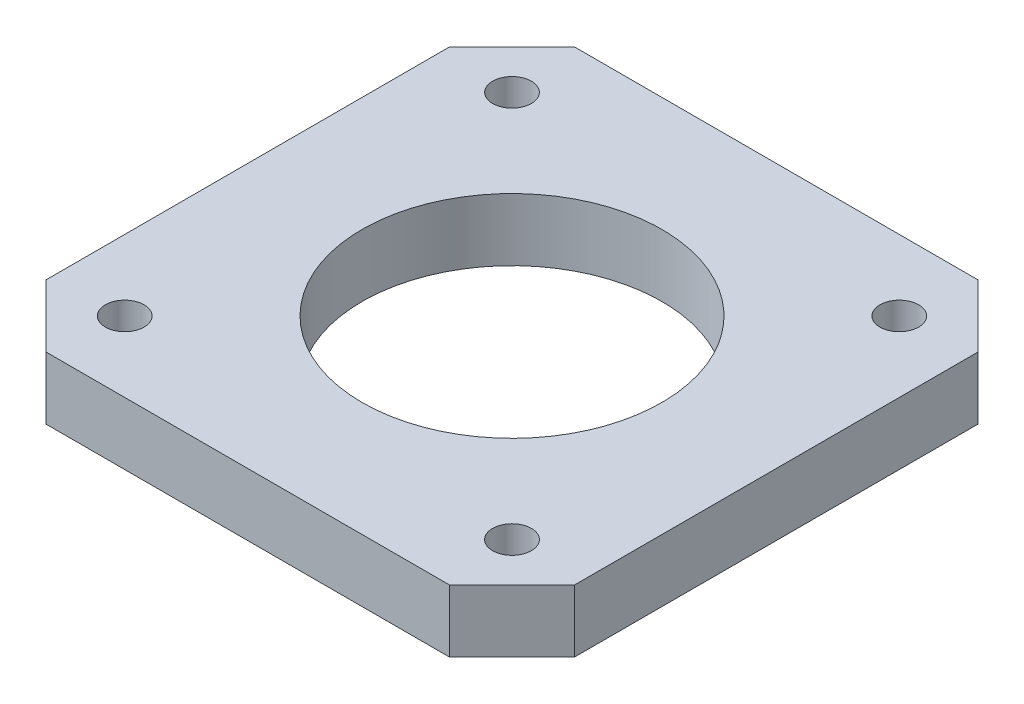
SolidWorks part; units mm, degrees
ref_plane "Front Plane" through (0, 0, 0) normal (0, 0, 1) x (1, 0, 0)
ref_plane "Top Plane" through (0, 0, 0) normal (0, 1, 0) x (1, 0, 0)
ref_plane "Right Plane" through (0, 0, 0) normal (1, 0, 0) x (0, 0, -1)
sketch "Sketch1" plane through (0, 0, 0) normal (0, 1, 0) x (1, 0, 0)
  line L1 (-15.5, 15.5) -> (15.5, 15.5) construction
  line L2 (-15.5, 15.5) -> (-15.5, -15.5) construction
  line L3 (-15.5, -15.5) -> (15.5, -15.5) construction
  line L4 (15.5, 15.5) -> (15.5, -15.5) construction
  line L5 (-15.5, 15.5) -> (15.5, -15.5) construction
  line L6 (-15.5, -15.5) -> (15.5, 15.5) construction
  line L7 (-21.15, 21.15) -> (21.15, 21.15)
  line L8 (-21.15, 21.15) -> (-21.15, -21.15)
  line L9 (-21.15, -21.15) -> (21.15, -21.15)
  line L10 (21.15, 21.15) -> (21.15, -21.15)
  line L11 (-21.15, 21.15) -> (21.15, -21.15) construction
  line L12 (-21.15, -21.15) -> (21.15, 21.15) construction
  circle A0 centre (-15.5, 15.5) radius 1.55
  circle A1 centre (15.5, 15.5) radius 1.55
  circle A2 centre (15.5, -15.5) radius 1.55
  circle A3 centre (-15.5, -15.5) radius 1.55
  circle A4 centre (0, 0) radius 12
  point P0 (0, 0)
  point P10 (0, 0)
  dimension "D2" = 3.1
  dimension "D4" = 24
  dimension "D1" = 31
  dimension "D3" = 42.3
extrude "Boss-Extrude1" add sketch "Sketch1" along normal blind 5
chamfer "Chamfer1" distance 5 angle 45 4 edges at (21.15, 2.5, -21.15) (21.15, 2.5, 21.15) (-21.15, 2.5, -21.15) (-21.15, 2.5, 21.15)
